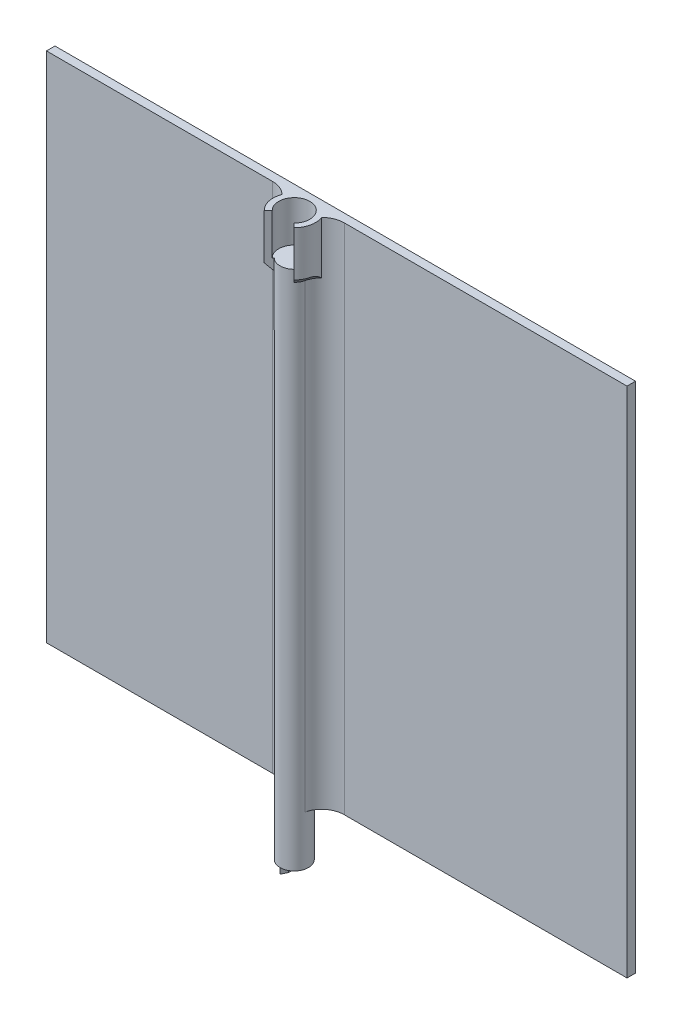
SolidWorks part; units mm, degrees
ref_plane "前视基准面" through (0, 0, 0) normal (0, 0, 1) x (1, 0, 0)
ref_plane "上视基准面" through (0, 0, 0) normal (0, 1, 0) x (1, 0, 0)
ref_plane "右视基准面" through (0, 0, 0) normal (1, 0, 0) x (0, 0, -1)
sketch "草图1" plane through (0, 0, 0) normal (0, 0, 1) x (1, 0, 0)
  line L1 (0, 0) -> (185, 0)
  line L2 (0, 0) -> (0, 170)
  line L3 (0, 170) -> (185, 170)
  line L4 (185, 0) -> (185, 170)
  dimension "D1" = 170
  dimension "D2" = 185
extrude "凸台-拉伸1" add sketch "草图1" along normal blind 3
sketch "草图2" plane through (0, 170, 0) normal (0, 1, 0) x (1, 0, 0)
  line L0 (185, -3) -> (0, -3) construction
  line L1 (87.5, -8) -> (87.5, -3)
  line L2 (97.5, -8) -> (97.5, -3)
  line L3 (87.5, -3) -> (97.5, -3)
  arc A0 (87.5, -8) -> (97.5, -8) centre (92.5, -8) ccw
  dimension "D1" = 10
  dimension "D2" = 5
extrude "凸台-拉伸2" add sketch "草图2" against normal up to surface (170 mm away) up to face at (92.5, 0, 1.5)
sketch "草图3" plane through (0, 170, 0) normal (0, 1, 0) x (1, 0, 0)
  circle A0 centre (92.5, -8) radius 5
extrude "凸台-拉伸3" add sketch "草图3" along normal blind 30
sketch "草图4" plane through (0, 0, 0) normal (0, -1, 0) x (1, 0, 0)
  circle A0 centre (92.5, 8) radius 5
  dimension "D1" = 10
extrude "凸台-拉伸4" add sketch "草图4" along normal blind 12.5
sketch "草图5" plane through (0, 200, 0) normal (0, 1, 0) x (1, 0, 0)
  line L1 (91.5, -11) -> (91.5, -5)
  line L2 (93.5, -11) -> (93.5, -5)
  line L6 (91.5, -5) -> (92.5, -3)
  line L7 (92.5, -3) -> (93.5, -5)
  line L8 (91.5, -11) -> (92.5, -13)
  line L9 (92.5, -13) -> (93.5, -11)
  circle A0 centre (92.5, -8) radius 5 construction
  arc A1 (97.5, -8) -> (87.5, -8) centre (92.5, -8) ccw construction
  point P1 (92.5, -8)
  dimension "D1" = 1
  dimension "D2" = 6
sketch "草图6" plane through (0, -12.5, 0) normal (0, -1, 0) x (1, 0, 0)
  line L0 (92.5, 13) -> (93.5, 11) construction
  line L1 (91.5, 11) -> (92.5, 13) construction
  line L2 (91.5, 5) -> (92.5, 3) construction
  line L3 (92.5, 3) -> (93.5, 5) construction
  line L4 (93.5, 11) -> (93.5, 5) construction
  line L5 (91.5, 11) -> (91.5, 5) construction
  line L6 (92.5, 13) -> (93.5, 11)
  line L7 (91.5, 11) -> (92.5, 13)
  line L8 (91.5, 5) -> (92.5, 3)
  line L9 (92.5, 3) -> (93.5, 5)
  line L10 (93.5, 11) -> (93.5, 5)
  line L11 (91.5, 11) -> (91.5, 5)
  circle A1 centre (92.5, 8) radius 5
  circle A2 centre (92.5, 8) radius 5
  dimension "D1" = 0
extrude "凸台-拉伸5" add sketch "草图6" along normal blind 2 contours L7 L11 L8 L9 L10 L6 region at (92.5, -12.5, 8)
fillet "圆角1" radius 8 2 edges at (97.5, 85, 3) (87.5, 85, 3)
sketch "草图7" plane through (0, 0, 0) normal (0, -1, 0) x (1, 0, 0)
  line L1 (185, 3) -> (205, 3)
  line L2 (185, 3) -> (185, 0)
  line L3 (185, 0) -> (205, 0)
  line L4 (205, 3) -> (205, 0)
  dimension "D1" = 3
  dimension "D2" = 20
extrude "凸台-拉伸6" add sketch "草图7" against normal up to surface (170 mm away) up to face at (92.5, 170, 2.6811)
sketch "草图8" plane through (0, 200, 0) normal (0, 1, 0) x (1, 0, 0)
  circle A1 centre (92.5, -8) radius 5
  circle A2 centre (92.5, -8) radius 5
  dimension "D1" = 0
extrude "切除-拉伸1" cut sketch "草图8" against normal up to surface (30 mm away) up to face at (97.5, 170, 2.6811)
sketch "草图9" plane through (0, 170, 0) normal (0, 1, 0) x (1, 0, 0)
  circle A1 centre (92.5, -8) radius 7.5
  arc A2 (87.635, -9.1538) -> (97.365, -9.1538) centre (92.5, -8) ccw construction
  dimension "D1" = 15
extrude "凸台-拉伸9" add sketch "草图9" along normal blind 16
sketch "草图11" plane through (0, 186, 0) normal (0, 1, 0) x (1, 0, 0)
  circle A0 centre (92.5, -8) radius 5.5
  dimension "D1" = 11
extrude "切除-拉伸2" cut sketch "草图11" against normal blind 12.5
sketch "草图12" plane through (0, 173.5, 0) normal (0, 1, 0) x (1, 0, 0)
  line L0 (93.7, -4.9528) -> (92.5, -2.5528)
  line L1 (92.5, -2.5528) -> (91.3, -4.9528)
  line L2 (91.3, -4.9528) -> (91.3, -11.0472)
  line L3 (91.3, -11.0472) -> (92.5, -13.4472)
  line L4 (92.5, -13.4472) -> (93.7, -11.0472)
  line L5 (93.7, -11.0472) -> (93.7, -4.9528)
extrude "切除-拉伸3" cut sketch "草图12" against normal blind 2
sketch "草图13" plane through (0, 170, 0) normal (0, -1, 0) x (1, 0, 0)
  line L0 (87.25, 13.3561) -> (89, 11.5707)
  line L1 (96, 11.5707) -> (97.75, 13.3561)
  arc A4 (99.5078, 5.3277) -> (85.4922, 5.3277) centre (92.5, 8) ccw
  arc A5 (85.4922, 5.3277) -> (87.635, 9.1538) centre (79.8509, 11) ccw
  arc A6 (97.365, 9.1538) -> (87.635, 9.1538) centre (92.5, 8) ccw
  arc A7 (97.365, 9.1538) -> (99.5078, 5.3277) centre (105.1491, 11) ccw
  arc A8 (97.75, 13.3561) -> (87.25, 13.3561) centre (92.5, 8) ccw
  arc A10 (96, 11.5707) -> (89, 11.5707) centre (92.5, 8) ccw
  dimension "D2" = 3.5
  dimension "D3" = 3.5
  dimension "D1" = 0
extrude "切除-拉伸4" cut sketch "草图13" against normal up to next
sketch "草图14" plane through (0, 170, 0) normal (0, 1, 0) x (1, 0, 0)
  line L5 (105.1491, -3) -> (205, -3)
  line L6 (205, -3) -> (205, 0)
  line L7 (205, 0) -> (0, 0)
  line L8 (0, 0) -> (0, -3)
  line L9 (0, -3) -> (79.8509, -3)
  line L10 (105.1491, -3) -> (205, -3)
  line L11 (205, -3) -> (205, 0)
  line L12 (205, 0) -> (0, 0)
  line L13 (0, 0) -> (0, -3)
  line L14 (0, -3) -> (79.8509, -3)
  arc A3 (99.5078, -5.3277) -> (85.4922, -5.3277) centre (92.5, -8) ccw
  arc A4 (105.1491, -3) -> (99.5078, -5.3277) centre (105.1491, -11) ccw
  arc A5 (85.4922, -5.3277) -> (79.8509, -3) centre (79.8509, -11) ccw
  arc A6 (99.5078, -5.3277) -> (85.4922, -5.3277) centre (92.5, -8) ccw
  arc A7 (105.1491, -3) -> (99.5078, -5.3277) centre (105.1491, -11) ccw
  arc A8 (85.4922, -5.3277) -> (79.8509, -3) centre (79.8509, -11) ccw
  dimension "D1" = 0
extrude "凸台-拉伸10" add sketch "草图14" along normal up to surface (16 mm away) up to face at (92.5, 186, 7.071)
chamfer "倒角1" distance 2.5 angle 45 4 edges at (96.8536, 170, 10.4589) (98.1691, 170, 7.0911) (86.8309, 170, 7.0911) (88.1464, 170, 10.4589)
sketch "草图15" plane through (0, 173.5, 0) normal (0, 1, 0) x (1, 0, 0)
  line L8 (96, -11.5707) -> (96.35, -11.9278)
  line L9 (88.65, -11.9278) -> (89, -11.5707)
  line L10 (92.2738, -12.9949) -> (91.3, -11.0472)
  line L11 (91.3, -11.0472) -> (91.3, -4.9528)
  line L12 (91.3, -4.9528) -> (92.5, -2.5528)
  line L13 (92.5, -2.5528) -> (93.7, -4.9528)
  line L14 (93.7, -4.9528) -> (93.7, -11.0472)
  line L15 (93.7, -11.0472) -> (92.7262, -12.9949)
  line L16 (96, -11.5707) -> (96.35, -11.9278)
  line L17 (88.65, -11.9278) -> (89, -11.5707)
  line L18 (92.2738, -12.9949) -> (91.3, -11.0472)
  line L19 (91.3, -11.0472) -> (91.3, -4.9528)
  line L20 (91.3, -4.9528) -> (92.5, -2.5528)
  line L21 (92.5, -2.5528) -> (93.7, -4.9528)
  line L22 (93.7, -4.9528) -> (93.7, -11.0472)
  line L23 (93.7, -11.0472) -> (92.7262, -12.9949)
  arc A3 (96.35, -11.9278) -> (88.65, -11.9278) centre (92.5, -8) ccw
  arc A4 (89, -11.5707) -> (92.2738, -12.9949) centre (92.5, -8) ccw
  arc A5 (92.7262, -12.9949) -> (96, -11.5707) centre (92.5, -8) ccw
  arc A6 (96.35, -11.9278) -> (88.65, -11.9278) centre (92.5, -8) ccw
  arc A7 (89, -11.5707) -> (92.2738, -12.9949) centre (92.5, -8) ccw
  arc A8 (92.7262, -12.9949) -> (96, -11.5707) centre (92.5, -8) ccw
  dimension "D1" = 0
extrude "切除-拉伸5" cut sketch "草图15" against normal blind 2
sketch "草图16" plane through (0, 0, 0) normal (0, -1, 0) x (1, 0, 0)
  line L5 (79.8509, 3) -> (0, 3)
  line L6 (0, 3) -> (0, 0)
  line L7 (0, 0) -> (205, 0)
  line L8 (205, 0) -> (205, 3)
  line L9 (205, 3) -> (105.1491, 3)
  line L10 (79.8509, 3) -> (0, 3)
  line L11 (0, 3) -> (0, 0)
  line L12 (0, 0) -> (205, 0)
  line L13 (205, 0) -> (205, 3)
  line L14 (205, 3) -> (105.1491, 3)
  arc A3 (87.635, 9.1538) -> (97.365, 9.1538) centre (92.5, 8) ccw
  arc A4 (79.8509, 3) -> (87.635, 9.1538) centre (79.8509, 11) ccw
  arc A5 (97.365, 9.1538) -> (105.1491, 3) centre (105.1491, 11) ccw
  arc A6 (87.635, 9.1538) -> (97.365, 9.1538) centre (92.5, 8) ccw
  arc A7 (79.8509, 3) -> (87.635, 9.1538) centre (79.8509, 11) ccw
  arc A8 (97.365, 9.1538) -> (105.1491, 3) centre (105.1491, 11) ccw
  dimension "D1" = 0
extrude "切除-拉伸6" cut sketch "草图16" against normal blind 5
